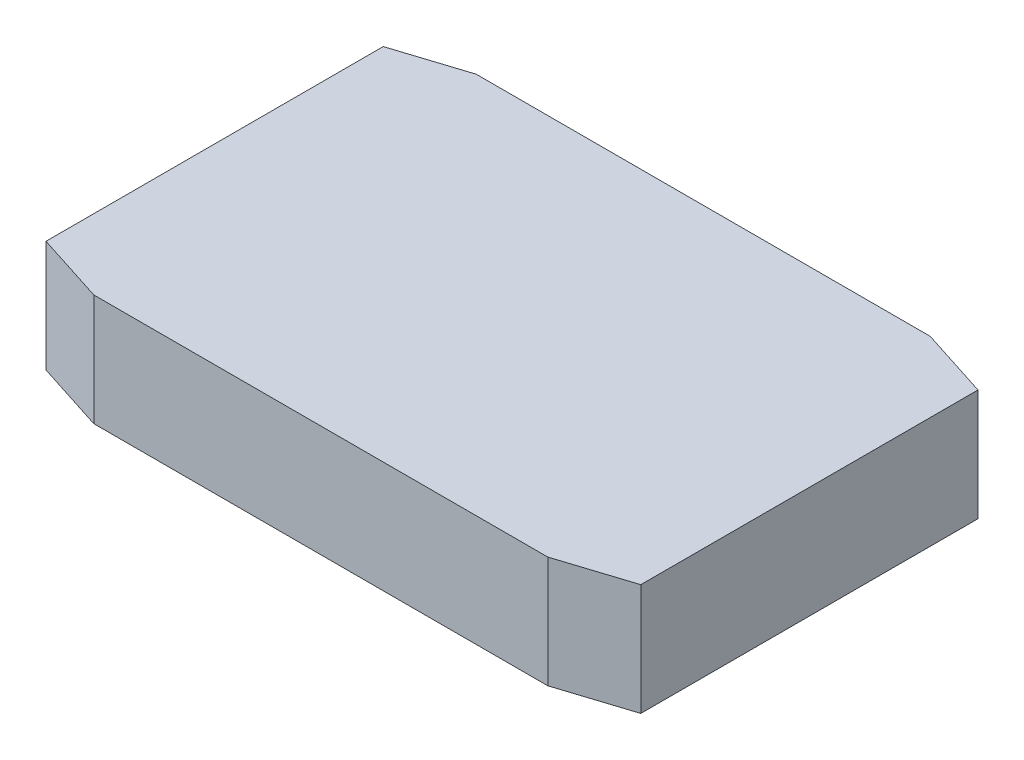
SolidWorks part; units mm, degrees
ref_plane "Front Plane" through (0, 0, 0) normal (0, 0, 1) x (1, 0, 0)
ref_plane "Top Plane" through (0, 0, 0) normal (0, 1, 0) x (1, 0, 0)
ref_plane "Right Plane" through (0, 0, 0) normal (1, 0, 0) x (0, 0, -1)
sketch "Sketch1" plane through (0, 0, 0) normal (0, 1, 0) x (1, 0, 0)
  line L1 (0, 0) -> (224, 0)
  line L2 (0, 0) -> (0, 144)
  line L3 (0, 144) -> (224, 144)
  line L4 (224, 0) -> (224, 144)
  dimension "D1" = 224
  dimension "D2" = 144
extrude "Boss-Extrude1" add sketch "Sketch1" along normal blind 42
sketch "Sketch2" plane through (0, 0, 0) normal (0, -1, 0) x (1, 0, 0)
  line L0 (0, 0) -> (224, 0) construction
  line L1 (24.5, -10.25) -> (199.5, -10.25)
  line L2 (24.5, -10.25) -> (24.5, -21.25)
  line L3 (24.5, -21.25) -> (199.5, -21.25)
  line L4 (199.5, -10.25) -> (199.5, -21.25)
  line L5 (0, -144) -> (0, 0) construction
  line L6 (24.5, -15.75) -> (0, -15.75) construction
  line L7 (199.5, -15.75) -> (224, -15.75) construction
  line L8 (224, 0) -> (224, -144) construction
  line L9 (0, -72) -> (224, -72) construction
  line L10 (24.5, -122.75) -> (199.5, -122.75)
  line L11 (199.5, -133.75) -> (199.5, -122.75)
  line L12 (24.5, -133.75) -> (199.5, -133.75)
  line L13 (24.5, -133.75) -> (24.5, -122.75)
  dimension "D1" = 10.25
  dimension "D2" = 11
  dimension "D3" = 24.5
extrude "Boss-Extrude2" add sketch "Sketch2" along normal blind 4.5 contours L13 L12 L11 L10 | L2 L3 L4 L1 region at (112, 0, -128.25)
ref_plane "Plane1" through (0, 0, -72) normal (0, 0, -1) x (-1, 0, 0)
ref_plane "Plane2" through (112, 0, 0) normal (1, 0, 0) x (0, 0, -1)
ref_plane "Plane3" through (0, 0, -72) normal (0, 0, -1) x (-1, 0, 0)
ref_plane "Plane4" through (0, 21, 0) normal (0, 1, 0) x (1, 0, 0)
ref_plane "Clearance" through (30, 0, 0) normal (-1, 0, 0) x (0, 0, 1)
ref_plane "Clearance1" through (194, 0, 0) normal (1, 0, 0) x (0, 0, -1)
chamfer "Chamfer1" distance 8.5 distance2 26.5 2 edges at (0, 21, 0) (224, 21, -144) first distance on face at (0, 21, -72) first distance on face at (224, 21, -72)
chamfer "Chamfer2" distance 26.5 distance2 8.5 2 edges at (0, 21, -144) (224, 21, 0) first distance on face at (98.75, 21, -144) first distance on face at (125.25, 21, 0)
